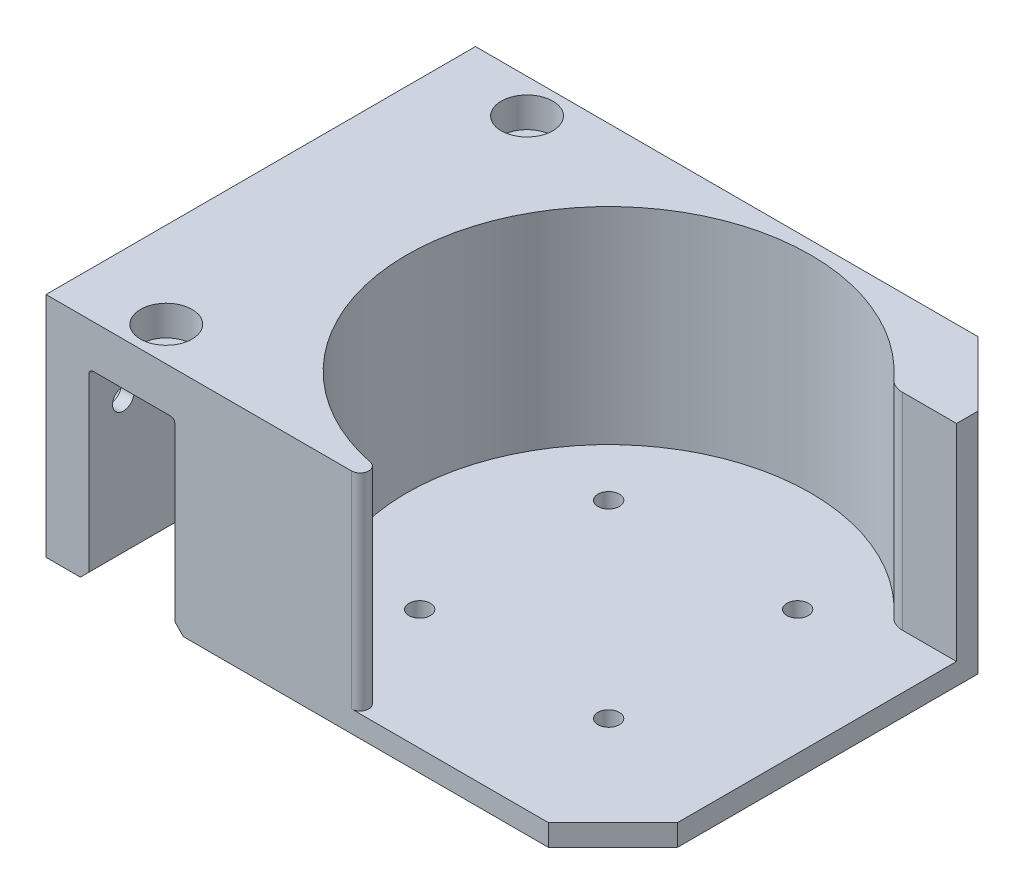
SolidWorks part; units mm, degrees
ref_plane "前视基准面" through (0, 0, 0) normal (0, 0, 1) x (1, 0, 0)
ref_plane "上视基准面" through (0, 0, 0) normal (0, 1, 0) x (1, 0, 0)
ref_plane "右视基准面" through (0, 0, 0) normal (1, 0, 0) x (0, 0, -1)
sketch "草图1" plane through (0, 0, 0) normal (0, 1, 0) x (1, 0, 0)
  line L1 (-51, 50) -> (51, 50)
  line L2 (-51, 50) -> (-51, -50)
  line L3 (-51, -50) -> (51, -50)
  line L4 (51, 50) -> (51, -50)
  line L5 (-51, 50) -> (51, -50) construction
  line L6 (-51, -50) -> (51, 50) construction
  point P0 (0, 0)
  dimension "D1" = 102
  dimension "D2" = 100
extrude "凸台-拉伸1" add sketch "草图1" along normal blind 53
sketch "草图2" plane through (0, 53, 0) normal (0, 1, 0) x (1, 0, 0)
  line L1 (23, 30) -> (51, 30)
  line L2 (23, 30) -> (23, -30)
  line L3 (23, -30) -> (51, -30)
  line L4 (51, 30) -> (51, -30)
  line L5 (23, 30) -> (51, -30) construction
  line L6 (23, -30) -> (51, 30) construction
  circle A0 centre (0, 0) radius 47
  point P3 (37, 0)
  line M6 (51, -50) -> (51, 50)
  dimension "D1" = 94
  dimension "D2" = 60
  dimension "D3" = 28
  dimension "D4" = 37
extrude "切除-拉伸1" cut sketch "草图2" against normal blind 48 contours L1 A0 L3 L2 | L3 A0 L1 L2 | A0 L3 L1 M6 region at (-7.2566, 53, 0) region at (33.5315, 53, 0) region at (43.5901, 53, -29.382)
sketch "草图3" plane through (0, 53, 0) normal (0, 1, 0) x (1, 0, 0)
  line L0 (-51, -50) -> (51, -50) construction
  line L1 (0, -50) -> (51, -50)
  line L2 (0, -50) -> (0, 0)
  line L3 (0, 0) -> (51, 0)
  line L4 (51, -50) -> (51, 0)
  line L5 (51, -30) -> (51, 30) construction
extrude "切除-拉伸2" cut sketch "草图3" against normal blind 48
sketch "草图4" plane through (0, 5, 0) normal (0, 1, 0) x (1, 0, 0)
  line L1 (-22, 22) -> (22, 22)
  line L2 (-22, 22) -> (-22, -22)
  line L3 (-22, -22) -> (22, -22)
  line L4 (22, 22) -> (22, -22)
  line L5 (-22, 22) -> (22, -22) construction
  line L6 (-22, -22) -> (22, 22) construction
  circle A0 centre (-22, 22) radius 2.5
  circle A1 centre (22, 22) radius 2.5
  circle A2 centre (22, -22) radius 2.5
  circle A3 centre (-22, -22) radius 2.5
  point P0 (0, 0)
  dimension "D3" = 5
  dimension "D4" = 5
  dimension "D5" = 5
  dimension "D6" = 5
  dimension "D1" = 44
  dimension "D2" = 44
extrude "切除-拉伸3" cut sketch "草图4" against normal blind 48 contours L4 A1 L1 | L1 A1 L4 | L1 A0 L2 | L2 A0 L1 | L2 A3 L3 | L3 A3 L2 | L4 A2 L3 | L3 A2 L4 region at (-22.3537, 5, -22.3537) region at (-20.939, 5, -20.939) region at (22.3537, 5, -22.3537) region at (20.939, 5, -20.939) region at (-20.939, 5, 20.939) region at (-22.3537, 5, 22.3537) region at (22.3537, 5, 22.3537) region at (20.939, 5, 20.939)
chamfer "倒角1" distance 15 angle 45 2 edges at (51, 2.5, 50) (51, 26.5, -50)
fillet "圆角2" radius 5 2 edges at (0, 29, 47) (36.1801, 29, -30)
sketch "草图5" plane through (-51, 0, 0) normal (-1, 0, 0) x (0, 0, 1)
  line L0 (50, 53) -> (50, 0) construction
  line L1 (-50, 53) -> (50, 53)
  line L2 (-50, 53) -> (-50, 43)
  line L3 (-50, 43) -> (50, 43)
  line L4 (50, 53) -> (50, 43)
  dimension "D1" = 10
extrude "凸台-拉伸2" add sketch "草图5" along normal blind 30
sketch "草图6" plane through (0, 43, 0) normal (0, -1, 0) x (1, 0, 0)
  line L0 (-81, -50) -> (-51, -50) construction
  line L1 (-81, 50) -> (-71, 50)
  line L2 (-81, 50) -> (-81, -50)
  line L3 (-81, -50) -> (-71, -50)
  line L4 (-71, 50) -> (-71, -50)
  dimension "D1" = 10
extrude "凸台-拉伸3" add sketch "草图6" along normal up to surface (43 mm away) up to face at (22, 0, 24.5)
fillet "圆角5" radius 2 1 edges at (0, 29, 50)
sketch "草图8" plane through (0, 43, 0) normal (0, -1, 0) x (1, 0, 0)
  line L0 (-71, 50) -> (-51, 50) construction
  line L1 (-51, -50) -> (-51, 50) construction
  line L3 (-71, -50) -> (-51, -50) construction
  line L4 (-71, -50) -> (-71, 50) construction
  circle A0 centre (-61, 42) radius 2.5
  circle A1 centre (-61, -42) radius 2.5
  dimension "D1" = 5
  dimension "D4" = 5
  dimension "D2" = 8
  dimension "D3" = 10
  dimension "D5" = 10
  dimension "D6" = 8
extrude "切除-拉伸4" cut sketch "草图8" against normal blind 30
sketch "草图9" plane through (0, 53, 0) normal (0, 1, 0) x (1, 0, 0)
  circle A0 centre (-61, 42) radius 6
  circle A1 centre (-61, -42) radius 6
  dimension "D1" = 12
  dimension "D2" = 12
extrude "切除-拉伸5" cut sketch "草图9" against normal blind 7
sketch "草图10" plane through (-71, 0, 0) normal (1, 0, 0) x (0, 0, -1)
  line L0 (50, 43) -> (-50, 43) construction
  line L1 (-50, 0) -> (-50, 43) construction
  line L2 (50, 0) -> (50, 43) construction
  circle A0 centre (-42, 33) radius 2.5
  circle A1 centre (42, 33) radius 2.5
  dimension "D2" = 5
  dimension "D4" = 5
  dimension "D1" = 10
  dimension "D3" = 8
  dimension "D5" = 8
  dimension "D6" = 10
extrude "切除-拉伸6" cut sketch "草图10" against normal blind 30
sketch "草图11" plane through (-81, 0, 0) normal (-1, 0, 0) x (0, 0, 1)
  circle A0 centre (-42, 33) radius 6
  circle A1 centre (42, 33) radius 6
  dimension "D1" = 12
  dimension "D2" = 12
extrude "切除-拉伸7" cut sketch "草图11" against normal blind 7
chamfer "倒角2" distance 2 angle 45 2 edges at (-71, 0, 0) (-51, 0, 0)
fillet "圆角7" radius 1 2 edges at (-71, 43, 0) (-51, 43, 0)
